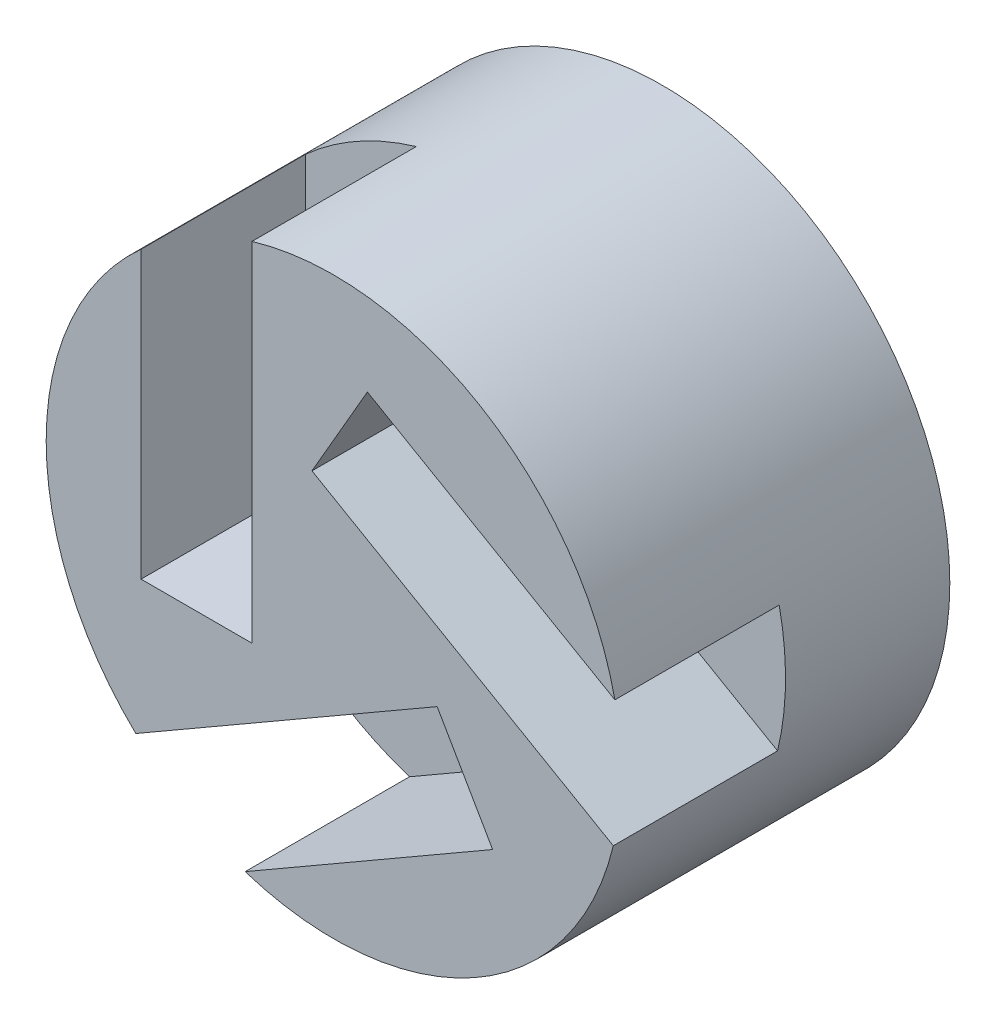
SolidWorks part; units mm, degrees
ref_plane "Alzado" through (0, 0, 0) normal (0, 0, 1) x (1, 0, 0)
ref_plane "Planta" through (0, 0, 0) normal (0, 1, 0) x (1, 0, 0)
ref_plane "Vista lateral" through (0, 0, 0) normal (1, 0, 0) x (0, 0, -1)
sketch "Croquis1" plane through (0, 0, 0) normal (0, 0, 1) x (1, 0, 0)
  line L0 (10.0823, -8.0631) -> (-4.9996, -16.7706)
  line L1 (1.9417, 12.7631) -> (17.0236, 4.0555)
  line L3 (6.4073, -1.6978) -> (10.0823, -8.0631)
  line L4 (6.4073, -1.6978) -> (-12.2679, -12.4799)
  line L5 (-1.7333, 6.3978) -> (1.9417, 12.7631)
  line L6 (-1.7333, 6.3978) -> (16.9419, -4.3844)
  line L9 (-4.674, -4.7) -> (-4.674, 16.8643)
  line L10 (-4.674, -4.7) -> (-12.024, -4.7)
  line L11 (-12.024, -4.7) -> (-12.024, 12.7151)
  circle A0 centre (0, 0) radius 17.5
  circle A1 centre (-8.349, 3.8) radius 1.625
  circle A2 centre (7.4654, 5.3304) radius 1.625
  circle A3 centre (0.8836, -9.1304) radius 1.625
  point P0 (0, 0)
extrude "Saliente-Extruir1" add sketch "Croquis1" along normal blind 10 contours L1 A0 L9 L10 L11 L4 L3 L0 L6 L5 region at (0, 0, 0)
sketch "Croquis3" plane through (0, 0, 0) normal (0, 0, -1) x (-1, 0, 0)
  circle A0 centre (0, 0) radius 17.5
  dimension "D1" = 35
extrude "Saliente-Extruir2" add sketch "Croquis3" along normal blind 10
extrude "Cortar-Extruir4" cut sketch "Croquis1<3>" against normal blind 10 contours A2 | A1 | A3 region at (-8.349, 3.8, 0) region at (7.4654, 5.3304, 0) region at (0.8836, -9.1304, 0)
sketch "Croquis1<3>" plane through (0, 0, 0) normal (0, 0, 1) x (1, 0, 0) same geometry as "Croquis1"
sketch "Croquis4" plane through (0, 0, 10) normal (0, 0, 1) x (1, 0, 0)
  line L0 (-4.974, 16.7782) -> (-4.974, -4.4)
  line L1 (-4.974, -4.4) -> (-11.724, -4.4)
  line L2 (-11.724, -4.7) -> (-11.724, 12.9922)
  line L6 (-12.0434, -12.6967) -> (6.2975, -2.1076)
  line L7 (6.2975, -2.1076) -> (9.6725, -7.9533)
  line L8 (9.6725, -7.9533) -> (-5.3896, -16.6494)
  line L9 (1.9417, 12.7631) -> (17.0236, 4.0555)
  line L10 (-4.674, 16.8643) -> (-4.674, -4.7)
  line L11 (-4.674, -4.7) -> (-12.024, -4.7)
  line L12 (-12.024, -4.7) -> (-12.024, 12.7151)
  line L13 (-12.2679, -12.4799) -> (6.4073, -1.6978)
  line L14 (6.4073, -1.6978) -> (10.0823, -8.0631)
  line L15 (10.0823, -8.0631) -> (-4.9996, -16.7706)
  line L16 (16.9419, -4.3844) -> (-1.7333, 6.3978)
  line L17 (-1.7333, 6.3978) -> (1.9417, 12.7631)
  line L18 (1.9417, 12.7631) -> (17.0236, 4.0555)
  line L19 (-4.674, 16.8643) -> (-4.674, -4.7)
  line L20 (-4.674, -4.7) -> (-12.024, -4.7)
  line L21 (-12.024, -4.7) -> (-12.024, 12.7151)
  line L22 (-12.2679, -12.4799) -> (6.4073, -1.6978)
  line L23 (6.4073, -1.6978) -> (10.0823, -8.0631)
  line L24 (10.0823, -8.0631) -> (-4.9996, -16.7706)
  line L25 (16.9419, -4.3844) -> (-1.7333, 6.3978)
  line L26 (-1.7333, 6.3978) -> (1.9417, 12.7631)
  line L27 (16.7611, 3.8606) -> (2.0515, 12.3533)
  line L28 (2.0515, 12.3533) -> (-1.3235, 6.5076)
  line L29 (-1.3235, 6.5076) -> (16.7462, -3.925)
  line L30 (17.1136, 3.6571) -> (2.0515, 12.3533)
  line L31 (2.0515, 12.3533) -> (-1.3235, 6.5076)
  line L32 (-1.3235, 6.5076) -> (17.0174, -4.0815)
  line L33 (-11.724, -4.4) -> (-11.724, 12.7151) construction
  line L34 (9.6725, -7.9533) -> (-5.1496, -16.5108) construction
  line L35 (-4.974, 16.8643) -> (-4.974, -4.4) construction
  line L36 (-12.1179, -12.7397) -> (6.2975, -2.1076) construction
  arc A1 (-4.674, 16.8643) -> (-12.024, 12.7151) centre (0, 0) ccw construction
  arc A2 (16.7462, -3.925) -> (16.7611, 3.8606) centre (0, 0) ccw
  arc A3 (17.0236, 4.0555) -> (-4.674, 16.8643) centre (0, 0) ccw
  arc A4 (-12.024, 12.7151) -> (-12.2679, -12.4799) centre (0, 0) ccw
  arc A5 (-4.9996, -16.7706) -> (16.9419, -4.3844) centre (0, 0) ccw
  arc A10 (-4.674, 16.8643) -> (-12.024, 12.7151) centre (0, 0) ccw
  arc A11 (-12.2679, -12.4799) -> (-4.9996, -16.7706) centre (0, 0) ccw construction
  arc A12 (16.9419, -4.3844) -> (17.0236, 4.0555) centre (0, 0) ccw construction
  arc A13 (-12.2679, -12.4799) -> (-4.9996, -16.7706) centre (0, 0) ccw
  arc A14 (16.9419, -4.3844) -> (17.0236, 4.0555) centre (0, 0) ccw
  line M21 (1.9417, 12.7631) -> (17.0236, 4.0555)
  line M23 (-4.674, 16.8643) -> (-4.674, -4.7)
  line M24 (-4.674, -4.7) -> (-12.024, -4.7)
  line M25 (-12.024, -4.7) -> (-12.024, 12.7151)
  line M27 (-12.2679, -12.4799) -> (6.4073, -1.6978)
  line M28 (6.4073, -1.6978) -> (10.0823, -8.0631)
  line M29 (10.0823, -8.0631) -> (-4.9996, -16.7706)
  line M31 (16.9419, -4.3844) -> (-1.7333, 6.3978)
  line M32 (-1.7333, 6.3978) -> (1.9417, 12.7631)
  dimension "D1" = 0
  dimension "D2" = 0.3
  dimension "D3" = 0.3
  dimension "D4" = 0.3
extrude "Saliente-Extruir3" add sketch "Croquis4" against normal blind 10 contours L30 A14 L32 L31 M21 M32 M31 | A13 L6 L7 L8 M27 M29 M28 | A10 L0 L1 L2 M23 M24 | L2 A10 M25 M24 region at (-4.7616, 16.6038, 10) region at (-11.8736, 4.0776, 10) region at (17.0449, 3.851, 10) region at (-2.7955, -7.3223, 10)
